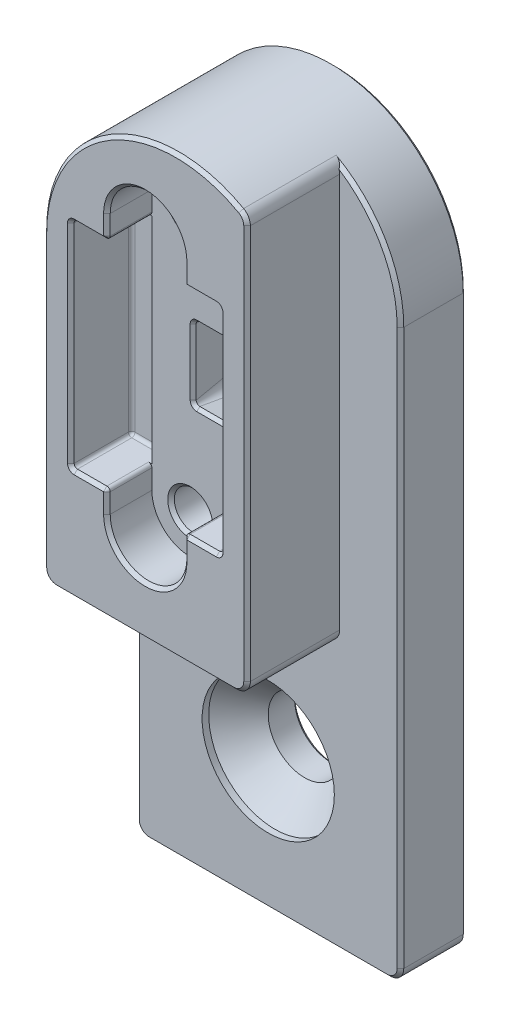
SolidWorks part; units mm, degrees
ref_plane "Front Plane" through (0, 0, 0) normal (0, 0, 1) x (1, 0, 0)
ref_plane "Top Plane" through (0, 0, 0) normal (0, 1, 0) x (1, 0, 0)
ref_plane "Right Plane" through (0, 0, 0) normal (1, 0, 0) x (0, 0, -1)
sketch "Sketch1" plane through (0, 0, 0) normal (0, 0, 1) x (1, 0, 0)
  line L0 (-21.8994, 0) -> (21.4746, 0) construction
  line L1 (0, 20.9985) -> (0, -16.0644) construction
  line L2 (-10, 10) -> (10, 10) construction
  line L3 (-10, 43) -> (10, 43)
  line L4 (-10, 43) -> (-10, -10)
  line L5 (-10, -10) -> (10, -10)
  line L6 (10, 43) -> (10, -10)
  line L7 (-10, 43) -> (10, -10) construction
  line L8 (-10, -10) -> (10, 43) construction
  line L9 (-10, 10) -> (10, -10) construction
  line L10 (-10, 10) -> (-10, -10) construction
  line L11 (-10, 10) -> (10, 43) construction
  circle A1 centre (0, 0) radius 2.75
  circle A2 centre (0, 33) radius 10
  point P4 (0, 16.5)
  point P12 (0, 0)
  point P13 (0, 26.5)
  dimension "D4" = 5.5
  dimension "D1" = 20
  dimension "D2" = 33
extrude "Boss-Extrude1" add sketch "Sketch1" along normal blind 5 contours L4 L5 L6 A1 | A2 region at (0, 33, 0) region at (0, 7.9113, 0)
hole_wizard "CSK for M5 Flat Head Machine Screw1" positions "Sketch3" profile "Sketch4" countersink size "M5" standard "ANSI Metric" end condition through all
sketch "Sketch3" plane through (0, 0, 5) normal (0, 0, 1) x (1, 0, 0)
  point P0 (0, 0)
sketch "Sketch4" plane through (0, 0, 5) normal (1, 0, 0) x (0, -1, 0)
  line L0 (0, 0) -> (0, 5)
  line L1 (0, 5) -> (2.75, 5)
  line L2 (2.75, 5) -> (2.75, 2.75)
  line L3 (2.75, 2.75) -> (5, 0.5)
  line L4 (5, 0.5) -> (5, 0)
  line L6 (5, 0) -> (0, 0)
  line L7 (-2.75, 2.75) -> (-5, 0.5) construction
  line L11 (0, -6.35) -> (0, 107.95) construction
  dimension "Thru Hole Dia." = 5.5
  dimension "Thru Hole Depth" = 5
  dimension "C'Sink Dia." = 10
  dimension "C'Sink Angle" = 90
  dimension "Head Clearance" = 0.5
sketch "Sketch5" plane through (0, 0, 5) normal (0, 0, 1) x (1, 0, 0)
  line L0 (0, 39.621) -> (0, -14.9634) construction
  line L1 (-10, 10) -> (10, 10) construction
  line L2 (-10, 33) -> (-10, -10) construction
  line L3 (10, 33) -> (10, -10) construction
  line L4 (-10, -10) -> (10, -10) construction
  line L5 (-11.4083, 43) -> (12.5744, 43) construction
  line L6 (-10, 10) -> (-10, 43) construction
  line L7 (-17.2391, 26.5) -> (-4.1577, 26.5) construction
  line L8 (-2.3, 52.2713) -> (-2.3, 37.4231) construction
  circle A0 centre (-2.3, 36.35) radius 1.45
  circle A1 centre (-2.3, 16.65) radius 1.45
  arc A3 (10, 33) -> (-10, 33) centre (0, 33) ccw construction
  point P16 (0, 43)
  point P18 (-10, 26.5)
  dimension "D2" = 2.9
  dimension "D1" = 19.7
  dimension "D3" = 20
  dimension "D4" = 2.3
extrude "Cut-Extrude1" cut sketch "Sketch5" against normal up to next
sketch "Sketch11" plane through (0, 0, 5) normal (0, 0, 1) x (1, 0, 0)
  line L0 (-2.3, 36.35) -> (-2.3, 16.65) construction
  line L1 (-10, 33) -> (-10, -10) construction
  line L2 (5.4, 43) -> (-10, 43)
  line L3 (5.4, 43) -> (5.4, 10)
  line L4 (5.4, 10) -> (-10, 10)
  line L5 (-10, 43) -> (-10, 10)
  line L6 (5.4, 43) -> (-10, 10) construction
  line L7 (5.4, 10) -> (-10, 43) construction
  line L11 (10, -10) -> (10, 33)
  line L12 (-10, 33) -> (-10, -10)
  line L13 (-10, -10) -> (10, -10)
  line L14 (10, -10) -> (10, 33)
  line L15 (-10, 33) -> (-10, -10)
  line L16 (-10, -10) -> (10, -10)
  arc A0 (10, 33) -> (-10, 33) centre (0, 33) ccw construction
  circle A1 centre (-2.3, 16.65) radius 1.45 construction
  circle A2 centre (-2.3, 36.35) radius 1.45 construction
  circle A3 centre (-2.3, 16.65) radius 1.45
  circle A4 centre (-2.3, 36.35) radius 1.45
  arc A6 (10, 33) -> (-10, 33) centre (0, 33) ccw
  arc A7 (10, 33) -> (-10, 33) centre (0, 33) ccw
  point P4 (-2.3, 26.5)
  circle M5 centre (-2.3, 36.35) radius 1.45
  circle M6 centre (-2.3, 16.65) radius 1.45
  arc M9 (10, 33) -> (-10, 33) centre (0, 33) ccw
  line M10 (-10, 33) -> (-10, -10)
  dimension "D1" = 0
extrude "Boss-Extrude3" add sketch "Sketch11" along normal blind 7 contours L4 L3 M9 M10 M6 M5 region at (-2.0881, 25.7559, 5)
sketch "Sketch6" plane through (0, 0, 12) normal (0, 0, 1) x (1, 0, 0)
  line L0 (-2.3, 36.35) -> (-2.3, 16.65) construction
  line L1 (-5.1394, 26.5) -> (1.0915, 26.5) construction
  line L2 (-5.2, 36.35) -> (-5.2, 34.625)
  line L3 (-7.925, 18.375) -> (3.325, 18.375)
  line L4 (-7.925, 18.375) -> (-7.925, 34.625)
  line L5 (-7.925, 34.625) -> (3.325, 34.625)
  line L6 (3.325, 18.375) -> (3.325, 34.625)
  line L7 (-7.925, 18.375) -> (3.325, 34.625) construction
  line L8 (-7.925, 34.625) -> (3.325, 18.375) construction
  line L9 (0.6, 36.35) -> (0.6, 34.625)
  line L10 (0.6, 16.65) -> (0.6, 18.375)
  line L11 (-5.2, 16.65) -> (-5.2, 18.375)
  circle A0 centre (-2.3, 36.35) radius 2.9
  circle A1 centre (-2.3, 16.65) radius 2.9
  point P6 (-2.3, 26.5)
  point P8 (-2.3, 26.5)
  dimension "D1" = 5.8
  dimension "D2" = 11.25
  dimension "D3" = 16.25
extrude "Cut-Extrude2" cut sketch "Sketch6" against normal blind 3.4 contours A0 L5 | A0 L2 L5 | A0 L5 L9 | L5 A0 | A1 L3 L11 | L3 A1 | L3 A1 | A1 L10 L3 | A1 L3 L6 L5 A0 L4 region at (-5.0327, 35.0473, 12) region at (-2.3, 36.7239, 12) region at (-2.3, 26.5, 12) region at (0.4327, 35.0473, 12) region at (-2.3, 34.1457, 12) region at (-5.0327, 17.9527, 12) region at (-2.3, 18.8543, 12) region at (-2.3, 16.2761, 12) region at (0.4327, 17.9527, 12)
sketch "Sketch7" plane through (0, 0, 8.6) normal (0, 0, 1) x (1, 0, 0)
  line L1 (-7.925, 34.625) -> (-5.2, 34.625)
  line L2 (-7.925, 34.625) -> (-7.925, 18.375)
  line L3 (-7.925, 18.375) -> (-5.2, 18.375)
  line L4 (-5.2, 34.625) -> (-5.2, 18.375)
extrude "Cut-Extrude3" cut sketch "Sketch7" against normal blind 1.2
sketch "Sketch8" plane through (0, 0, 8.6) normal (0, 0, 1) x (1, 0, 0)
  line L0 (-7.925, 26.5) -> (3.325, 26.5) construction
  line L1 (-7.925, 34.625) -> (-7.925, 18.375) construction
  line L4 (-2.05, 29.25) -> (1.45, 29.25)
  line L5 (-2.05, 29.25) -> (-2.05, 23.75)
  line L6 (-2.05, 23.75) -> (1.45, 23.75)
  line L7 (1.45, 29.25) -> (1.45, 23.75)
  line L8 (-2.05, 29.25) -> (1.45, 23.75) construction
  line L9 (-2.05, 23.75) -> (1.45, 29.25) construction
  line L10 (3.325, 18.375) -> (3.325, 34.625) construction
  line L11 (-2.3, 36.35) -> (-2.3, 16.65) construction
  point P6 (-0.3, 26.5)
  dimension "D1" = 3.5
  dimension "D2" = 5.5
  dimension "D3" = 2
extrude "Cut-Extrude4" cut sketch "Sketch8" against normal up to next
fillet "Fillet1" radius 1 5 edges at (10, -10, 2.5) (-10, -10, 2.5) (5.4, 41.4167, 8.5) (5.4, 10, 8.5) (-10, 10, 8.5)
fillet "Fillet3" radius 0.25 16 edges at (-2.05, 29.25, 4.3) (1.45, 29.25, 4.3) (1.45, 23.75, 4.3) (-2.05, 23.75, 4.3) (-6.5625, 34.625, 7.4) (-5.2, 26.5, 7.4) (-6.5625, 18.375, 7.4) (-7.925, 26.5, 7.4) (-5.2, 34.625, 10.3) (-7.925, 34.625, 9.7) (-7.925, 18.375, 9.7) (-5.2, 18.375, 10.3) (0.6, 18.375, 10.3) (3.325, 18.375, 10.3) (3.325, 34.625, 10.3) (0.6, 34.625, 10.3)
chamfer "Chamfer3" distance 1.5 angle 80 8 edges at (1.45, 26.5, 0) (1.3768, 23.8232, 0) (1.3768, 29.1768, 0) (-0.3, 23.75, 0) (-0.3, 29.25, 0) (-1.9768, 23.8232, 0) (-1.9768, 29.1768, 0) (-2.05, 26.5, 0) first distance on face at (-0.3, 26.5, 0)
chamfer "Chamfer2" distance 0.25 angle 45 60 edges at (-0.85, 16.65, 8.6) (-2.05, 26.5, 8.6) (-1.9768, 23.8232, 8.6) (-1.9768, 29.1768, 8.6) (-0.3, 23.75, 8.6) (-0.3, 29.25, 8.6) (1.3768, 23.8232, 8.6) (1.3768, 29.1768, 8.6) (1.45, 26.5, 8.6) (-0.85, 36.35, 8.6) (2.75, 0, 0) (-0.85, 16.65, 0) (-0.85, 36.35, 0) (9.7071, -9.7071, 0) (10, 12, 0) (0, -10, 0) (0, 43, 0) (-9.7071, -9.7071, 0) (-10, 12, 0) (-9.7071, -9.7071, 5) (-10, 1, 5) (0, -10, 5) (8.6281, 38.0553, 5) (9.7071, -9.7071, 5) (10, 12, 5) (-7.8518, 34.5518, 12) (-7.925, 26.5, 12) (-7.8518, 18.4482, 12) (-6.5625, 18.375, 12) (-5.2732, 18.3018, 12) (-5.2, 17.3875, 12) (-2.3, 13.75, 12) (0.6, 17.3875, 12) (0.6732, 18.3018, 12) (1.9625, 18.375, 12) (3.2518, 18.4482, 12) (3.325, 26.5, 12) (3.2518, 34.5518, 12) (1.9625, 34.625, 12) (0.6732, 34.6982, 12) (0.6, 35.6125, 12) (-2.3, 39.25, 12) (-5.2, 35.6125, 12) (-5.2732, 34.6982, 12) (-6.5625, 34.625, 12) (5.1071, 10.2929, 12) (-2.3, 10, 12) (-9.7071, 10.2929, 12) (-10, 22, 12) (-5.0553, 41.6281, 12) (5.2628, 41.3566, 12) (5.4, 25.9256, 12) (2.95, 26.5, 0) (2.4374, 30.2374, 0) (2.4374, 22.7626, 0) (-0.3, 30.75, 0) (-0.3, 22.25, 0) (-3.0374, 30.2374, 0) (-3.0374, 22.7626, 0) (-3.55, 26.5, 0) first distance on face at (-0.85, 16.65, 0) first distance on face at (-2.05, 26.5, 8.5535) first distance on face at (-1.9509, 23.8491, 8.5535) first distance on face at (-1.9509, 29.1509, 8.5535) first distance on face at (-0.3, 23.75, 8.5535) first distance on face at (-0.3, 29.25, 8.5535) first distance on face at (1.3509, 23.8491, 8.5535) first distance on face at (1.3509, 29.1509, 8.5535) first distance on face at (1.45, 26.5, 8.5535) first distance on face at (-0.85, 36.35, 0) first distance on face at (2.75, 0, 0) first distance on face at (9.6036, -9.6036, 2.5) first distance on face at (10, 12, 2.5) first distance on face at (0, -10, 2.5) first distance on face at (1.4103, 38.4011, 5.6667) first distance on face at (-9.6036, -9.6036, 2.5) first distance on face at (-10, 11.6667, 5.6667) first distance on face at (-7.8259, 34.5259, 9.825) first distance on face at (-7.925, 26.5, 9.825) first distance on face at (-7.8259, 18.4741, 9.825) first distance on face at (-6.1083, 18.375, 9.4167) first distance on face at (-5.2991, 18.2759, 10.3) first distance on face at (-5.2, 17.3875, 10.3) first distance on face at (-2.3, 15.2, 10.3) first distance on face at (0.6, 17.3875, 10.3) first distance on face at (0.6991, 18.2759, 10.3) first distance on face at (1.9625, 18.375, 10.3) first distance on face at (3.2259, 18.4741, 10.3) first distance on face at (3.325, 26.5, 10.3) first distance on face at (3.2259, 34.5259, 10.3) first distance on face at (1.9625, 34.625, 10.3) first distance on face at (0.6991, 34.7241, 10.3) first distance on face at (0.6, 35.6125, 10.3) first distance on face at (-2.3, 37.8, 10.3) first distance on face at (-5.2, 35.6125, 10.3) first distance on face at (-5.2991, 34.7241, 10.3) first distance on face at (-6.1083, 34.625, 9.4167) first distance on face at (5.0036, 10.3964, 8.5) first distance on face at (-2.3, 10, 8.5) first distance on face at (-9.6036, 10.3964, 8.5) first distance on face at (5.2036, 41.322, 8.5) first distance on face at (5.4, 25.9256, 8.5) first distance on face at (2.2, 26.5, 4.2535) first distance on face at (1.8036, 29.6036, 4.2535) first distance on face at (1.8036, 23.3964, 4.2535) first distance on face at (-0.3, 30, 4.2535) first distance on face at (-0.3, 23, 4.2535) first distance on face at (-2.4036, 29.6036, 4.2535) first distance on face at (-2.4036, 23.3964, 4.2535) first distance on face at (-2.8, 26.5, 4.2535)
sketch "Sketch9" [suppressed] plane through (0, 0, 0) normal (0, 0, -1) x (-1, 0, 0)
  line L0 (-9.75, 33) -> (-9.75, -9) construction
  line L1 (-9, -9.75) -> (9, -9.75) construction
  line L2 (9.75, -9) -> (9.75, 33) construction
  line L3 (-9.75, 33) -> (-9.75, -9)
  line L4 (-9, -9.75) -> (9, -9.75)
  line L5 (9.75, -9) -> (9.75, 33)
  arc A0 (-9.75, -9) -> (-9, -9.75) centre (-9, -9) ccw construction
  arc A1 (9, -9.75) -> (9.75, -9) centre (9, -9) ccw construction
  arc A2 (9.75, 33) -> (-9.75, 33) centre (0, 33) ccw construction
  arc A3 (-9.75, -9) -> (-9, -9.75) centre (-9, -9) ccw
  arc A4 (9, -9.75) -> (9.75, -9) centre (9, -9) ccw
  arc A5 (9.75, 33) -> (-9.75, 33) centre (0, 33) ccw
  circle A8 centre (0, 0) radius 5 construction
  circle A9 centre (0, 0) radius 5
extrude "Boss-Extrude2" [suppressed] add sketch "Sketch9" against normal up to surface (5 mm away) up to face at (1.1605, 10.7996, 5)
